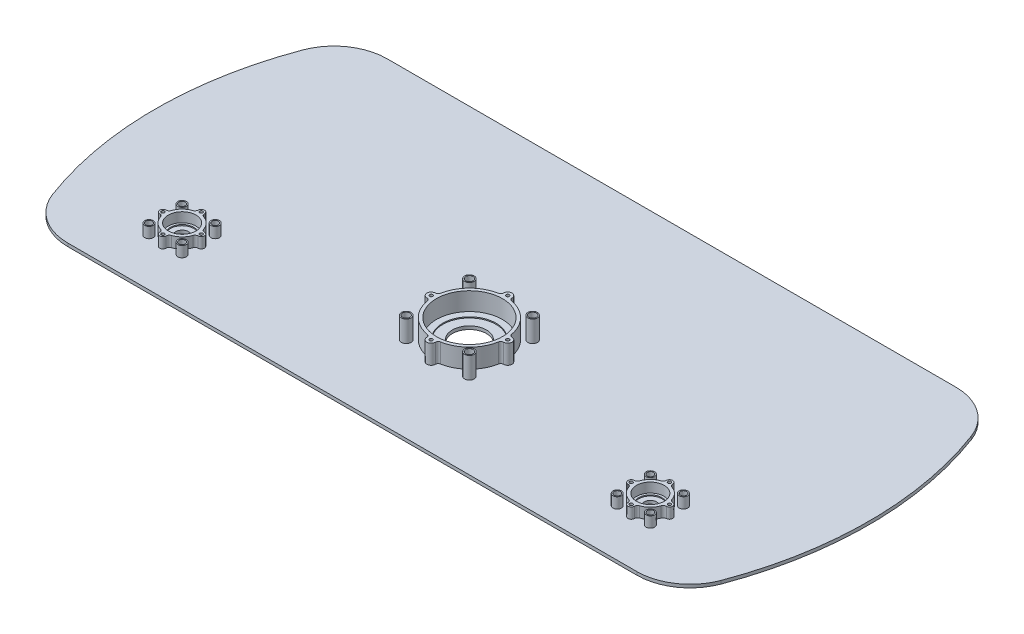
SolidWorks part; units mm, degrees
ref_plane "Front Plane" through (0, 0, 0) normal (0, 0, 1) x (1, 0, 0)
ref_plane "Top Plane" through (0, 0, 0) normal (0, 1, 0) x (1, 0, 0)
ref_plane "Right Plane" through (0, 0, 0) normal (1, 0, 0) x (0, 0, -1)
sketch "Sketch1" plane through (0, 0, 0) normal (0, 1, 0) x (1, 0, 0)
  line L1 (-267.3181, 150) -> (267.3181, 150)
  line L3 (-267.3181, -150) -> (267.3181, -150)
  line L5 (-300, 150) -> (300, -150) construction
  line L6 (-300, -150) -> (300, 150) construction
  arc A0 (314.1486, 117.5186) -> (314.1486, -117.5186) centre (0, 0) cw
  arc A1 (-314.1486, 117.5186) -> (-314.1486, -117.5186) centre (0, 0) ccw
  arc A2 (314.1486, 117.5186) -> (267.3181, 150) centre (267.3181, 100) ccw
  arc A3 (267.3181, -150) -> (314.1486, -117.5186) centre (267.3181, -100) ccw
  arc A4 (-267.3181, -150) -> (-314.1486, -117.5186) centre (-267.3181, -100) cw
  arc A5 (-267.3181, 150) -> (-314.1486, 117.5186) centre (-267.3181, 100) ccw
  circle A6 centre (0, -40) radius 130 construction
  circle A7 centre (-220, -90) radius 60 construction
  circle A8 centre (220, -90) radius 60 construction
  point P0 (0, 0)
  point P19 (0, -40)
  dimension "D3" = 50
  dimension "D5" = 260
  dimension "D6" = 120
  dimension "D7" = 120
  dimension "D1" = 300
  dimension "D2" = 600
  dimension "D4" = 40
  dimension "D8" = 90
  dimension "D9" = 220
  dimension "D10" = 90
  dimension "D11" = 220
extrude "Boss-Extrude1" add sketch "Sketch1" along normal blind 3
sketch "Sketch2" plane through (0, 3, 0) normal (0, 1, 0) x (1, 0, 0)
  circle A0 centre (220, -90) radius 60 construction
  circle A1 centre (-220, -90) radius 60 construction
  circle A2 centre (220, -90) radius 60 construction
  circle A3 centre (-220, -90) radius 60 construction
  circle A4 centre (-220, -90) radius 6
  circle A5 centre (220, -90) radius 6
  circle A6 centre (0, -40) radius 17.5
  circle A7 centre (220, -90) radius 11
  circle A8 centre (220, -90) radius 13
  circle A9 centre (-220, -90) radius 13
  circle A10 centre (-220, -90) radius 11
  circle A13 centre (-220, -90) radius 16
  circle A14 centre (220, -90) radius 16
  circle A15 centre (238, -90) radius 1.5
  arc A16 (235.8611, -87.8964) -> (235.8611, -92.1036) centre (238, -90) cw
  arc A17 (222.1036, -105.8611) -> (217.8964, -105.8611) centre (220, -108) cw
  circle A18 centre (220, -108) radius 1.5
  arc A19 (204.1389, -92.1036) -> (204.1389, -87.8964) centre (202, -90) cw
  circle A20 centre (202, -90) radius 1.5
  arc A21 (217.8964, -74.1389) -> (222.1036, -74.1389) centre (220, -72) cw
  circle A22 centre (220, -72) radius 1.5
  arc A23 (202, -87) -> (204.8114, -84.9696) centre (202, -84.0385) ccw
  arc A24 (202, -93) -> (204.8114, -95.0304) centre (202, -95.9615) cw
  arc A25 (223, -72) -> (225.0304, -74.8114) centre (225.9615, -72) ccw
  arc A26 (217, -72) -> (214.9696, -74.8114) centre (214.0385, -72) cw
  arc A27 (238, -93) -> (235.1886, -95.0304) centre (238, -95.9615) ccw
  arc A28 (238, -87) -> (235.1886, -84.9696) centre (238, -84.0385) cw
  arc A29 (217, -108) -> (214.9696, -105.1886) centre (214.0385, -108) ccw
  arc A30 (223, -108) -> (225.0304, -105.1886) centre (225.9615, -108) cw
  point P36 (220, -90)
  point P61 (220, -90)
  dimension "D1" = 35
  dimension "D2" = 26
  dimension "D3" = 22
  dimension "D4" = 26
  dimension "D5" = 22
  dimension "D6" = 12
  dimension "D7" = 12
  dimension "D8" = 3
  dimension "D9" = 3
  dimension "D10" = 3
  dimension "D11" = 18
  dimension "D12" = 4
  dimension "D13" = 4
extrude "Cut-Extrude1" cut sketch "Sketch2" against normal blind 10 contours A4 | A5 region at (-220, 3, 90) region at (220, 3, 90)
extrude "Boss-Extrude2" add sketch "Sketch2<3>" along normal blind 1 from surface contours A9 A10 | A8 A7 region at (207.3677, 3, 90) region at (-232.6323, 3, 90) starting at face at (-220, 3, 96)
sketch "Sketch2<3>" plane through (0, 3, 0) normal (0, 1, 0) x (1, 0, 0) same geometry as "Sketch2"
extrude "Boss-Extrude3" add sketch "Sketch2<4>" along normal blind 10 from surface contours A14 A8 | A19 A14 A20 | A21 A14 A22 | A16 A14 A15 | A17 A14 A18 | A23 A19 A14 | A19 A24 A14 | A25 A21 A14 | A21 A26 A14 | A16 A28 A14 | A27 A16 A14 | A17 A30 A14 | A29 A17 A14 region at (235.5137, 3, 91.0243) region at (236.0441, 3, 88.9407) region at (236.2045, 3, 86.846) region at (236.2045, 3, 93.154) region at (223.154, 3, 73.7955) region at (223.154, 3, 106.2045) region at (220, 3, 73.921) region at (222.694, 3, 106.871) region at (216.846, 3, 73.7955) region at (216.846, 3, 106.2045) region at (203.7955, 3, 86.846) region at (203.7955, 3, 93.154) region at (203.921, 3, 90) starting at face at (220, 3, 103)
sketch "Sketch2<4>" plane through (0, 3, 0) normal (0, 1, 0) x (1, 0, 0) same geometry as "Sketch2"
sketch "Sketch3" plane through (0, 3, 0) normal (0, 1, 0) x (1, 0, 0)
  circle A0 centre (0, -40) radius 16
  circle A1 centre (0, -40) radius 25
  circle A2 centre (0, -40) radius 31
  circle A3 centre (0, -40) radius 34
  circle A4 centre (36, -40) radius 1.5
  arc A6 (33.8333, -43.3624) -> (33.8333, -36.6376) centre (36, -40) ccw
  arc A7 (-3.3624, -73.8333) -> (3.3624, -73.8333) centre (0, -76) ccw
  circle A8 centre (0, -76) radius 1.5
  arc A9 (-33.8333, -36.6376) -> (-33.8333, -43.3624) centre (-36, -40) ccw
  circle A10 centre (-36, -40) radius 1.5
  arc A11 (3.3624, -6.1667) -> (-3.3624, -6.1667) centre (0, -4) ccw
  circle A12 centre (0, -4) radius 1.5
  arc A13 (-36, -36) -> (-33.4426, -33.8689) centre (-36, -33.4) ccw
  arc A14 (-36, -44) -> (-33.4426, -46.1311) centre (-36, -46.6) cw
  arc A15 (4, -4) -> (6.1311, -6.5574) centre (6.6, -4) ccw
  arc A16 (-4, -4) -> (-6.1311, -6.5574) centre (-6.6, -4) cw
  arc A17 (36, -44) -> (33.4426, -46.1311) centre (36, -46.6) ccw
  arc A18 (36, -36) -> (33.4426, -33.8689) centre (36, -33.4) cw
  arc A19 (-4, -76) -> (-6.1311, -73.4426) centre (-6.6, -76) ccw
  arc A20 (4, -76) -> (6.1311, -73.4426) centre (6.6, -76) cw
  point P25 (0, -40)
  point P50 (0, -40)
  dimension "D1" = 32
  dimension "D2" = 62
  dimension "D3" = 3
  dimension "D4" = 50
  dimension "D5" = 4
  dimension "D7" = 3
  dimension "D6" = 36
  dimension "D8" = 4
  dimension "D9" = 4
extrude "Cut-Extrude8" cut sketch "Sketch3" against normal blind 10 contours A0 region at (0, 3, 40)
extrude "Boss-Extrude4" add sketch "Sketch3<3>" along normal blind 1 from surface contours A2 A1 region at (-30.1232, 3, 40) starting at face at (0, 3, 56)
sketch "Sketch3<3>" plane through (0, 3, 0) normal (0, 1, 0) x (1, 0, 0) same geometry as "Sketch3"
extrude "Boss-Extrude5" add sketch "Sketch3<4>" along normal blind 18 from surface contours A3 A2 | A3 A6 A4 | A3 A7 A8 | A3 A9 A10 | A3 A11 A12 | A13 A9 A3 | A9 A14 A3 | A11 A16 A3 | A15 A11 A3 | A17 A6 A3 | A6 A18 A3 | A7 A20 A3 | A19 A7 A3 region at (32.9978, 3, 41.6356) region at (34.0592, 3, 38.3117) region at (34.2416, 3, 35.7431) region at (34.2416, 3, 44.2569) region at (4.2569, 3, 5.7584) region at (4.2569, 3, 74.2416) region at (0, 3, 5.899) region at (3.7404, 3, 74.8992) region at (-4.2569, 3, 5.7584) region at (-4.2569, 3, 74.2416) region at (-34.2416, 3, 35.7431) region at (-34.2416, 3, 44.2569) region at (-34.101, 3, 40) starting at face at (0, 3, 71)
sketch "Sketch3<4>" plane through (0, 3, 0) normal (0, 1, 0) x (1, 0, 0) same geometry as "Sketch3"
mirror "Mirror1" about plane through (0, 0, 0) normal (1, 0, 0) of "Boss-Extrude3"
sketch "Sketch4" plane through (0, 3, 0) normal (0, 1, 0) x (1, 0, 0)
  line B0 (0, -40) -> (-78.0469, 38.0469) construction
  circle B1 centre (-29.6985, -10.3015) radius 2
  circle B2 centre (-29.6985, -10.3015) radius 4.5
  circle B3 centre (-29.6985, -10.3015) radius 3.5
  circle B4 centre (29.6985, -10.3015) radius 4.5
  circle B5 centre (29.6985, -10.3015) radius 3.5
  circle B6 centre (29.6985, -10.3015) radius 2
  circle B7 centre (29.6985, -69.6985) radius 4.5
  circle B8 centre (29.6985, -69.6985) radius 3.5
  circle B9 centre (29.6985, -69.6985) radius 2
  circle B10 centre (-29.6985, -69.6985) radius 4.5
  circle B11 centre (-29.6985, -69.6985) radius 3.5
  circle B12 centre (-29.6985, -69.6985) radius 2
  circle B13 centre (-29.6985, -10.3015) radius 6.5
  arc B14 (-31.7007, -27.4352) -> (-34.2947, -14.8977) centre (-42.5371, -23.1401) ccw
  arc B15 (-12.5648, -8.2993) -> (-25.1023, -5.7053) centre (-16.8599, 2.5371) cw
  arc B16 (12.5648, -8.2993) -> (25.1023, -5.7053) centre (16.8599, 2.5371) ccw
  arc B17 (31.7007, -27.4352) -> (34.2947, -14.8977) centre (42.5371, -23.1401) cw
  circle B18 centre (29.6985, -10.3015) radius 6.5
  arc B19 (31.7007, -52.5648) -> (34.2947, -65.1023) centre (42.5371, -56.8599) ccw
  arc B20 (12.5648, -71.7007) -> (25.1023, -74.2947) centre (16.8599, -82.5371) cw
  circle B21 centre (29.6985, -69.6985) radius 6.5
  arc B22 (-12.5648, -71.7007) -> (-25.1023, -74.2947) centre (-16.8599, -82.5371) ccw
  arc B23 (-31.7007, -52.5648) -> (-34.2947, -65.1023) centre (-42.5371, -56.8599) cw
  circle B24 centre (-29.6985, -69.6985) radius 6.5
  circle B25 centre (0, -40) radius 34.1
  circle B26 centre (3.6047, -60.6883) radius 2.7
  circle B27 centre (-19.7189, -32.7776) radius 2.7
  circle B28 centre (16.1143, -26.5341) radius 2.7
  circle B29 centre (0, -40) radius 6.5
sketch_block_instance "Block2-1"
sketch_block "Block2" parameters "D1"=4, "D2"=7, "D3"=9, "D4"=13
sketch_block_instance "Block1-1"
sketch_block "Block1"
extrude "Boss-Extrude6" add sketch "Sketch4" along normal blind 20 contours B4 B5 | B5 B6 | B2 B3 | B3 B1 | B7 B8 | B8 B9 | B10 B11 | B11 B12 region at (-34.0712, 3, 10.3015) region at (-33.0995, 3, 10.3015) region at (25.3258, 3, 10.3015) region at (26.2975, 3, 10.3015) region at (25.3258, 3, 69.6985) region at (26.2975, 3, 69.6985) region at (-34.0712, 3, 69.6985) region at (-33.0995, 3, 69.6985)
extrude "Cut-Extrude9" cut sketch "Sketch4<3>" against normal blind 5 from surface contours B3 B1 | B5 B6 | B8 B9 | B11 B12 region at (-33.0995, 3, 10.3015) region at (26.2975, 3, 10.3015) region at (26.2975, 3, 69.6985) region at (-33.0995, 3, 69.6985) starting at face at (-29.6985, 23, 14.8015)
sketch "Sketch4<3>" plane through (0, 3, 0) normal (0, 1, 0) x (1, 0, 0) same geometry as "Sketch4"
sketch "Sketch5" plane through (0, 3, 0) normal (0, 1, 0) x (1, 0, 0)
  circle B0 centre (204.4437, -74.4437) radius 1.5
  circle B1 centre (204.4437, -74.4437) radius 3
  circle B2 centre (204.4437, -74.4437) radius 4
  circle B3 centre (204.4437, -105.5563) radius 1.5
  arc B4 (200.5546, -101.6673) -> (208.3327, -109.4454) centre (204.4437, -105.5563) ccw
  arc B5 (218.4477, -105.824) -> (208.3327, -109.4454) centre (217.2205, -118.3332) ccw
  arc B6 (218.4477, -105.824) -> (221.5523, -105.824) centre (220, -90) ccw
  arc B7 (231.6673, -109.4454) -> (221.5523, -105.824) centre (222.7795, -118.3332) ccw
  arc B8 (231.6673, -109.4454) -> (239.4454, -101.6673) centre (235.5563, -105.5563) ccw
  arc B9 (235.824, -91.5523) -> (239.4454, -101.6673) centre (248.3332, -92.7795) ccw
  arc B10 (235.824, -91.5523) -> (235.824, -88.4477) centre (220, -90) ccw
  arc B11 (239.4454, -78.3327) -> (235.824, -88.4477) centre (248.3332, -87.2205) ccw
  arc B12 (239.4454, -78.3327) -> (231.6673, -70.5546) centre (235.5563, -74.4437) ccw
  arc B13 (221.5523, -74.176) -> (231.6673, -70.5546) centre (222.7795, -61.6668) ccw
  arc B14 (221.5523, -74.176) -> (218.4477, -74.176) centre (220, -90) ccw
  arc B15 (208.3327, -70.5546) -> (218.4477, -74.176) centre (217.2205, -61.6668) ccw
  arc B16 (208.3327, -70.5546) -> (200.5546, -78.3327) centre (204.4437, -74.4437) ccw
  arc B17 (204.176, -88.4477) -> (200.5546, -78.3327) centre (191.6668, -87.2205) ccw
  arc B18 (204.176, -88.4477) -> (204.176, -91.5523) centre (220, -90) ccw
  arc B19 (200.5546, -101.6673) -> (204.176, -91.5523) centre (191.6668, -92.7795) ccw
  circle B20 centre (204.4437, -105.5563) radius 3
  circle B21 centre (204.4437, -105.5563) radius 4
  circle B22 centre (235.5563, -105.5563) radius 1.5
  circle B23 centre (235.5563, -105.5563) radius 3
  circle B24 centre (235.5563, -105.5563) radius 4
  circle B25 centre (235.5563, -74.4437) radius 1.5
  circle B26 centre (235.5563, -74.4437) radius 3
  circle B27 centre (235.5563, -74.4437) radius 4
sketch_block_instance "Block3-1"
sketch_block "Block3"
extrude "Boss-Extrude7" add sketch "Sketch5" along normal blind 10 contours B27 B26 | B26 B25 | B2 B1 | B1 B0 | B24 B23 | B23 B22 | B20 B3 | B21 B20 region at (201.5285, 3, 74.4437) region at (200.5568, 3, 74.4437) region at (201.5285, 3, 105.5563) region at (200.5568, 3, 105.5563) region at (232.6412, 3, 105.5563) region at (231.6695, 3, 105.5563) region at (232.6412, 3, 74.4437) region at (231.6695, 3, 74.4437)
extrude "Cut-Extrude10" cut sketch "Sketch5<3>" against normal blind 5 from surface contours B20 B3 | B1 B0 | B26 B25 | B23 B22 region at (201.5285, 3, 74.4437) region at (201.5285, 3, 105.5563) region at (232.6412, 3, 105.5563) region at (232.6412, 3, 74.4437) starting at face at (235.5563, 13, 109.5563)
sketch "Sketch5<3>" plane through (0, 3, 0) normal (0, 1, 0) x (1, 0, 0) same geometry as "Sketch5"
mirror "Mirror2" about plane through (0, 0, 0) normal (1, 0, 0) of "Boss-Extrude7", "Cut-Extrude10"
sketch "Sketch7" plane through (0, 0, 0) normal (0, -1, 0) x (1, 0, 0)
  point P0 (0, 0)
  line B0 (220, 61) -> (-220, 61)
  line B1 (220, 119) -> (-220, 119)
  line B2 (220, 121) -> (-220, 121)
  line B3 (220, 59) -> (-220, 59)
  arc B4 (220, 119) -> (220, 61) centre (220, 90) cw
  arc B5 (-220, 119) -> (-220, 61) centre (-220, 90) ccw
  arc B6 (-220, 121) -> (-220, 59) centre (-220, 90) ccw
  arc B7 (220, 121) -> (220, 59) centre (220, 90) cw
  circle B8 centre (0, 115.25) radius 2
  circle B9 centre (0, 64.75) radius 2
  arc B10 (-3.3072, 119) -> (3.3072, 119) centre (0, 115.25) ccw
  arc B11 (-3.3072, 61) -> (3.3072, 61) centre (0, 64.75) cw
  circle B12 centre (0, 115.25) radius 3.5
  circle B13 centre (0, 64.75) radius 3.5
sketch_block_instance "Block5-1"
sketch_block "Block5" parameters "D4"=4, "D7"=4, "D1"=440, "D2"=29, "D3"=29, "D5"=7, "D6"=3, "D8"=8.5, "D9"=3.75, "D10"=8.5, "D11"=3.75, "D12"=2
